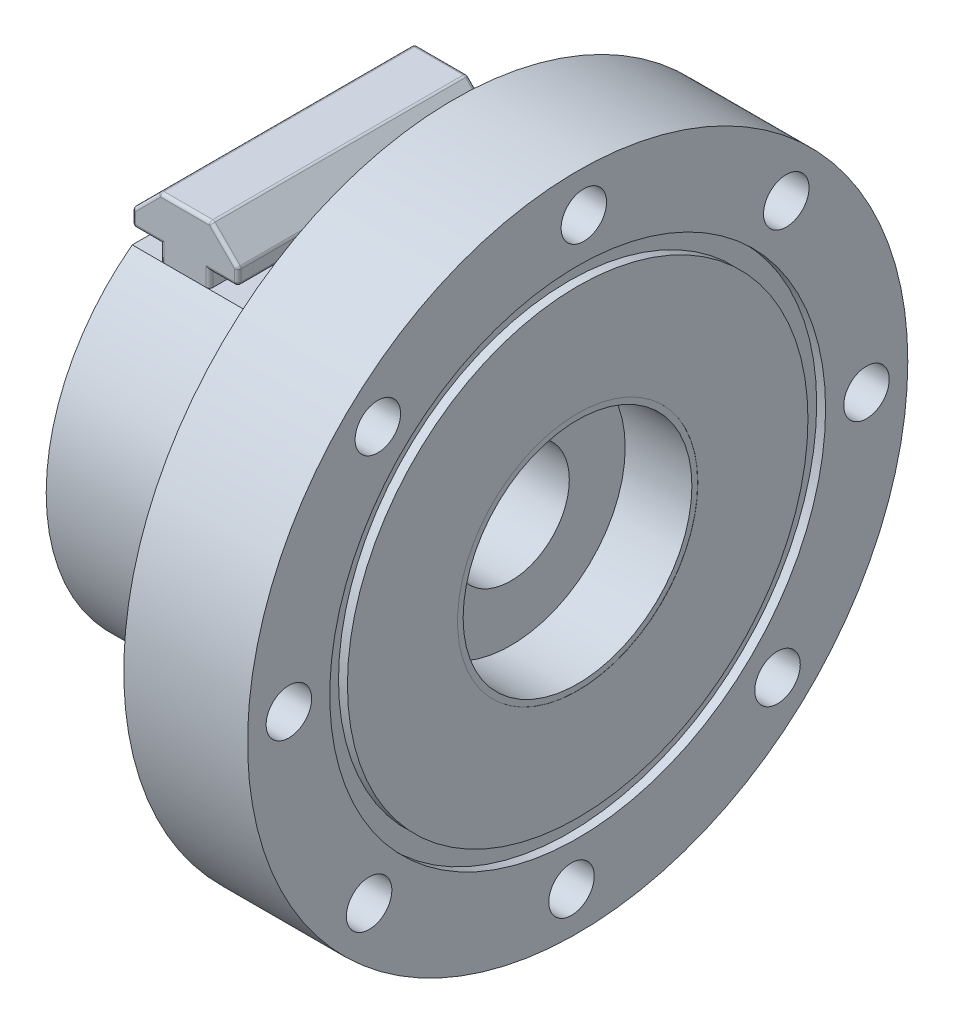
SolidWorks part; units mm, degrees
ref_plane "Front Plane" through (0, 0, 0) normal (0, 0, 1) x (1, 0, 0)
ref_plane "Top Plane" through (0, 0, 0) normal (0, 1, 0) x (1, 0, 0)
ref_plane "Right Plane" through (0, 0, 0) normal (1, 0, 0) x (0, 0, -1)
sketch "Main sketch" plane through (0, 0, 0) normal (0, 0, 1) x (1, 0, 0)
  line L0 (0, 9) -> (0, 20.005)
  line L1 (0, 20.005) -> (-8, 20.005)
  line L2 (-8, 20.005) -> (-8, 22.545)
  line L3 (-8, 33.02) -> (16.637, 33.02)
  line L4 (16.637, 33.02) -> (16.637, 50.8)
  line L5 (16.637, 50.8) -> (35.687, 50.8)
  line L6 (35.687, 50.8) -> (35.687, 38.1508)
  line L7 (35.687, 38.1508) -> (34.3154, 38.1508)
  line L8 (34.3154, 38.1508) -> (34.3154, 35.433)
  line L9 (34.3154, 35.433) -> (35.687, 35.433)
  line L10 (35.687, 35.433) -> (35.687, 18.4912)
  line L11 (35.687, 18.4912) -> (35.6616, 18.4912)
  line L12 (35.6616, 18.4912) -> (35.6616, 17.6022)
  line L13 (35.6616, 17.6022) -> (25.4, 17.6022)
  line L14 (25.4, 17.6022) -> (25.4, 9)
  line L15 (25.4, 9) -> (0, 9)
  line L16 (0, 0) -> (0, 9) construction
  line L17 (-8, 22.545) -> (-13.08, 22.545)
  line L18 (-13.08, 22.545) -> (-13.08, 33.02)
  line L19 (-13.08, 33.02) -> (-8, 33.02)
  point P20 (35.0012, 35.433)
  dimension "D1" = 9
  dimension "D2" = 20.005
  dimension "D4" = 17.6022
  dimension "D5" = 8
  dimension "D6" = 50.8
  dimension "D7" = 18.4912
  dimension "D11" = 25.4
  dimension "D12" = 10.2616
  dimension "D13" = 33.02
  dimension "D14" = 19.05
  dimension "D10" = 1.3716
  dimension "D15" = 5.08
  dimension "D16" = 2.54
  dimension "D3" = 180
  dimension "D17" = 0.0254
  dimension "D18" = 0.0254
  dimension "D8" = 38.1508
  dimension "D9" = 2.7178
ref_axis "Axis1" through (71.9501, 0, 0) along (-1, 0, 0)
revolve "Revolve1" add sketch "Main sketch" angle 360 about axis through (71.9501, 0, 0) along (-1, 0, 0)
sketch "Sketch2" plane through (35.687, 0, 0) normal (1, 0, 0) x (0, 0, -1)
  circle A0 centre (0, 0) radius 44.45 construction
  point P0 (0, 0)
  point P3 (-44.4399, 0.9486)
  point P4 (-32.0945, -30.753)
  point P7 (-0.9486, -44.4399)
  point P8 (30.753, -32.0945)
  point P9 (44.4399, -0.9486)
  point P10 (32.0945, 30.753)
  point P11 (0.9486, 44.4399)
  point P12 (-30.753, 32.0945)
  point P13 (0, 0)
  point P16 (0, 0)
  dimension "D2" = 88.9
  dimension "D1" = 8
hole_wizard "M6 Clearance Hole1" positions "Sketch2" profile "Sketch3" hole size "M6" standard "ISO" end condition through all
sketch "Sketch3" plane through (35.687, 0, 0) normal (0, 1, 0) x (0, 0, -1)
  line L0 (0, 0) -> (0, 48.767)
  line L1 (0, 48.767) -> (3.5, 48.767)
  line L2 (3.5, 48.767) -> (3.5, 0)
  line L5 (3.5, 0) -> (0, 0)
  line L11 (0, -6.35) -> (0, 107.95) construction
  dimension "Thru Hole Dia." = 7
  dimension "Thru Hole Depth" = 48.767
ref_plane "Plane1" through (0, 0, 33.02) normal (0, 0, 1) x (1, 0, 0)
ref_plane "Plane2" through (0, 33.02, 0) normal (0, 1, 0) x (1, 0, 0)
ref_plane "Plane3" through (0, 0, -33.02) normal (0, 0, -1) x (-1, 0, 0)
sketch "Sketch4" plane through (0, 33.02, 0) normal (0, 1, 0) x (1, 0, 0)
  line L0 (-13.08, -33.02) -> (16.637, -33.02) construction
  line L1 (16.637, 33.02) -> (16.637, -33.02) construction
  line L2 (16.637, 33.02) -> (-13.08, 33.02) construction
  line L4 (-13.08, -33.02) -> (16.637, -33.02)
  line L5 (16.637, 33.02) -> (16.637, -33.02)
  line L6 (16.637, 33.02) -> (-13.08, 33.02)
  line L8 (-13.08, 33.02) -> (-13.08, -33.02) construction
  line L9 (-13.08, 33.02) -> (-13.08, -33.02)
extrude "Cut-Extrude1" cut sketch "Sketch4" against normal blind 6.5786
ref_plane "Plane4" through (0, 0, -19.7781) normal (0, 0, 1) x (1, 0, 0)
ref_plane "Plane5" through (0, 0, 19.7781) normal (0, 0, -1) x (-1, 0, 0)
sketch "Sketch5" plane through (0, 0, 19.7781) normal (0, 0, -1) x (-1, 0, 0)
  line L0 (13.08, 26.4414) -> (-16.637, 26.4414) construction
  line L1 (13.08, 26.4414) -> (-16.637, 26.4414)
  line L2 (1.1912, 26.4414) -> (1.1912, 28.8684)
  line L3 (1.1912, 28.8684) -> (-3.176, 28.8684)
  line L4 (-3.176, 28.8684) -> (-3.176, 31.3274)
  line L5 (-3.176, 31.3274) -> (0.9888, 35.4922)
  line L6 (0.9888, 35.4922) -> (8.9152, 35.4922)
  line L7 (4.952, 35.4922) -> (4.952, 26.4414) construction
  line L8 (8.7128, 26.4414) -> (1.1912, 26.4414)
  line L9 (8.7128, 26.4414) -> (8.7128, 28.8684)
  line L10 (8.7128, 28.8684) -> (13.08, 28.8684)
  line L11 (13.08, 28.8684) -> (13.08, 31.3274)
  line L12 (13.08, 31.3274) -> (8.9152, 35.4922)
  line L14 (13.08, -33.02) -> (13.08, 26.4414) construction
  dimension "D1" = 3.7608
  dimension "D2" = 2.427
  dimension "D3" = 135
  dimension "D4" = 6.6238
  dimension "D5" = 8.128
  dimension "D6" = 7.9264
extrude "Boss-Extrude1" add sketch "Sketch5" along normal up to surface (39.5562 mm away) contours L7 L6 L5 L4 L3 L2 L8 | L6 L7 L1 L9 L10 L11 L12 region at (-8.2215, 31.1122, 19.7781) region at (-1.6825, 31.1122, 19.7781) up to plane "Plane4"
fillet "Fillet1" radius 0.508 24 edges at (-4.952, 35.4922, -19.7781) (-1.1912, 27.6549, 19.7781) (3.176, 30.0979, 19.7781) (0.9924, 28.8684, 19.7781) (1.0936, 33.4098, 19.7781) (-4.952, 35.4922, 19.7781) (-10.8964, 28.8684, 19.7781) (-8.7128, 27.6549, 19.7781) (-1.1912, 27.6549, -19.7781) (-8.7128, 27.6549, -19.7781) (-10.8964, 28.8684, -19.7781) (-10.9976, 33.4098, -19.7781) (-8.9152, 35.4922, 0) (-10.9976, 33.4098, 19.7781) (-13.08, 30.0979, 19.7781) (-13.08, 31.3274, 0) (-13.08, 28.8684, 0) (-13.08, 30.0979, -19.7781) (1.0936, 33.4098, -19.7781) (3.176, 30.0979, -19.7781) (0.9924, 28.8684, -19.7781) (-0.9888, 35.4922, 0) (3.176, 31.3274, 0) (3.176, 28.8684, 0)
mirror "Mirror1" about plane through (0, 0, 0) normal (0, 1, 0) of "Fillet1", "Boss-Extrude1", "Cut-Extrude1"
equation "\"Shaft_OD\"= 17mm'outer diameter of shaft"
equation "\"O_Ring_ID\"= 2.864in"
equation "\"O_Ring_CS\"= .070in'cross section"
equation "\"Bearing_OD\"= 40.01mm"
equation "\"Bearing_Depth\"= 8mm'depth bearing goes into the casing"
equation "\"Stationary_Face_Seal_OD\"= 1.386in"
equation "\"Flange_Dia\"= 4in"
equation "\"Screw_Dia\"= 6mm"
equation "\"Seal_Space\"= .3in"
equation "\"D1@Main sketch\"=\"Shaft_OD\" / 2 + .5mm"
equation "\"D2@Main sketch\" = \"Bearing_OD\" / 2"
equation "\"D4@Main sketch\" = \"Stationary_Face_Seal_OD\" / 2"
equation "\"D5@Main sketch\" = \"Bearing_Depth\""
equation "\"D6@Main sketch\" = \"Flange_Dia\" / 2"
equation "\"Seal_Area_Dia\"= 37mm"
equation "\"D7@Main sketch\"=\"Seal_space_Dia\"/2"
equation "\"Face_Seal_Height\"= 0.404in"
equation "\"D12@Main sketch\" = \"Face_Seal_Height\""
equation "\"Housing_OR\"= 1.3in'Outer radius of housing"
equation "\"D10@Main sketch\"=.054"
equation "\"D2@Sketch2\"=\"Flange_Dia\"-\"Screw_offset\""
equation "\"Screw_offset\"= .5in'offset of screws from flange OD."
equation "\"Seal_space_Dia\"= \"Stationary_Face_Seal_OD\" + .07'diameter of the space for the face seal"
equation "\"D8@Main sketch\"=(\"O_Ring_ID\"+2*\"O_Ring_CS\")/2"
equation "\"Groove_width\"=0.107"
equation "\"D9@Main sketch\"=\"Groove_width\""
